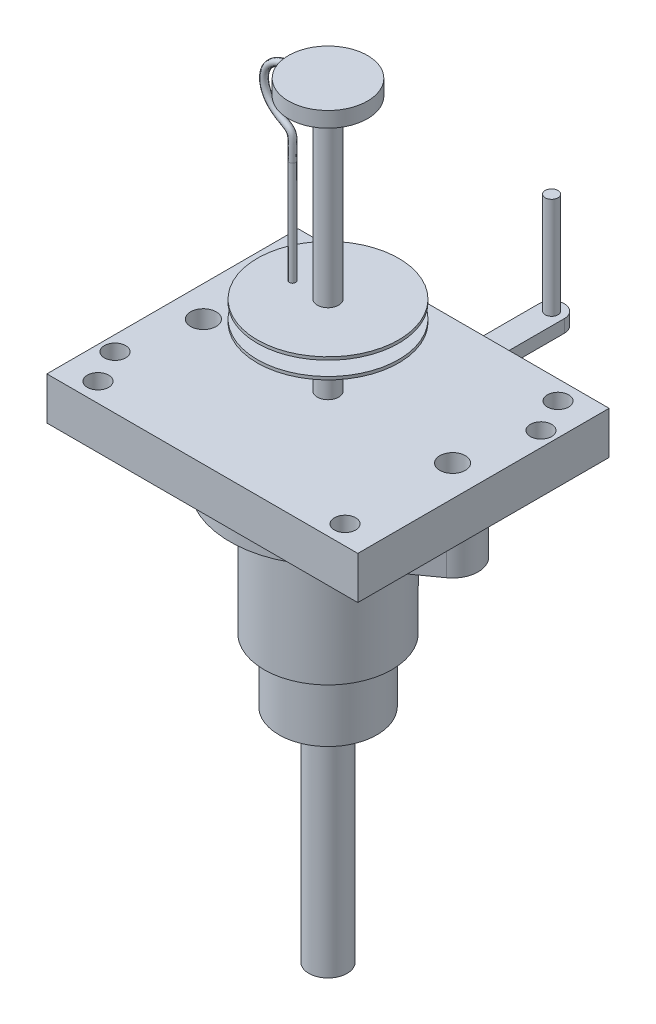
SolidWorks part; units mm, degrees
ref_plane "Front Plane" through (0, 0, 0) normal (0, 0, 1) x (1, 0, 0)
ref_plane "Top Plane" through (0, 0, 0) normal (0, 1, 0) x (1, 0, 0)
ref_plane "Right Plane" through (0, 0, 0) normal (1, 0, 0) x (0, 0, -1)
sketch "Sketch1" plane through (0, 0, 0) normal (0, 1, 0) x (1, 0, 0)
  line L1 (-36.5, -29.5) -> (36.5, -29.5)
  line L2 (-36.5, -29.5) -> (-36.5, 29.5)
  line L3 (-36.5, 29.5) -> (36.5, 29.5)
  line L4 (36.5, -29.5) -> (36.5, 29.5)
  line L5 (-36.5, -29.5) -> (36.5, 29.5) construction
  line L6 (-36.5, 29.5) -> (36.5, -29.5) construction
  point P0 (0, 0)
  dimension "D1" = 59
  dimension "D2" = 73
extrude "Boss-Extrude1" add sketch "Sketch1" against normal blind 10
sketch "Sketch2" plane through (0, 0, 0) normal (0, 1, 0) x (1, 0, 0)
  circle A0 centre (0, 0) radius 2.5
  dimension "D1" = 5
extrude "Boss-Extrude2" add sketch "Sketch2" along normal blind 60
sketch "Sketch3" plane through (0, 60, 0) normal (0, 1, 0) x (1, 0, 0)
  circle A0 centre (0, 0) radius 9.275
  dimension "D1" = 18.55
extrude "Boss-Extrude3" add sketch "Sketch3" along normal blind 3.6
ref_plane "Plane1" through (0, 14, 0) normal (0, 1, 0) x (1, 0, 0)
sketch "Sketch4" plane through (0, 14, 0) normal (0, 1, 0) x (1, 0, 0)
  circle A0 centre (0, 0) radius 16.6
  dimension "D1" = 33.2
extrude "Boss-Extrude4" add sketch "Sketch4" along normal blind 0.7
ref_plane "Plane2" through (0, 18, 0) normal (0, 1, 0) x (1, 0, 0)
sketch "Sketch5" plane through (0, 18, 0) normal (0, 1, 0) x (1, 0, 0)
  circle A1 centre (0, 0) radius 16.6 construction
  circle A2 centre (0, 0) radius 16.6
extrude "Boss-Extrude5" add sketch "Sketch5" along normal blind 0.7
sketch "Sketch7" plane through (0, -10, 0) normal (0, -1, 0) x (1, 0, 0)
  line L0 (32.25, -10.1714) -> (32.25, 9.148) construction
  line L1 (-19.7854, 27.5) -> (-31.5, 27.5) construction
  line L2 (-31.5, 21.4228) -> (-31.5, 27.5) construction
  line L3 (-36.5, -29.5) -> (-36.5, 29.5) construction
  line L4 (-36.5, 29.5) -> (36.5, 29.5) construction
  line L5 (0, 0) -> (-68.4596, 0) construction
  line L6 (0, 0) -> (0, -32.3752) construction
  line L7 (35.5, -19.5) -> (35.5, -7.1912) construction
  line L8 (26.5899, -19.5) -> (35.5, -19.5) construction
  line L9 (36.5, -29.5) -> (-36.5, -29.5) construction
  line L10 (36.5, 29.5) -> (36.5, -29.5) construction
  line L11 (-32.25, -10.1714) -> (-32.25, 9.148) construction
  line L12 (-35.5, 19.5) -> (-35.5, 7.1912) construction
  line L13 (-26.5899, 19.5) -> (-35.5, 19.5) construction
  circle A0 centre (-29, 25) radius 2.5
  circle A1 centre (29, 25) radius 2.5
  circle A2 centre (-29, -25) radius 2.5
  circle A3 centre (29, -25) radius 2.5
  circle A4 centre (33, -17) radius 2.5
  circle A5 centre (29.25, 0) radius 3
  circle A7 centre (-29.25, 0) radius 3
  circle A8 centre (-33, 17) radius 2.5
  dimension "D1" = 5
  dimension "D2" = 5
  dimension "D4" = 5
  dimension "D7" = 6
  dimension "D3" = 2
  dimension "D5" = 10
  dimension "D6" = 1
  dimension "D8" = 58.5
  dimension "D9" = 2
  dimension "D10" = 64.5
  dimension "D11" = 1
  dimension "D12" = 10
extrude "Cut-Extrude1" cut sketch "Sketch7" against normal up to surface (10 mm away) up to face at (0, 0, -2.5)
sketch "Sketch8" plane through (0, -10, 0) normal (0, -1, 0) x (1, 0, 0)
  line L0 (0, 0) -> (0, -27.931) construction
  line L1 (32.7372, 4.8826) -> (13.3675, 18.7166)
  line L2 (0, 0) -> (-51.9039, 0) construction
  line L3 (32.7372, -4.8826) -> (13.3675, -18.7166)
  line L4 (-32.7372, 4.8826) -> (-13.3675, 18.7166)
  line L5 (-32.7372, -4.8826) -> (-13.3675, -18.7166)
  arc A0 (13.3675, 18.7166) -> (-13.3675, 18.7166) centre (0, 0) ccw
  circle A1 centre (-29.25, 0) radius 3 construction
  arc A3 (-32.7372, 4.8826) -> (-32.7372, -4.8826) centre (-29.25, 0) ccw
  arc A4 (32.7372, 4.8826) -> (32.7372, -4.8826) centre (29.25, 0) cw
  arc A5 (-13.3675, -18.7166) -> (13.3675, -18.7166) centre (0, 0) ccw
  circle A6 centre (29.25, 0) radius 3 construction
  circle A7 centre (29.25, 0) radius 3
  circle A8 centre (-29.25, 0) radius 3
  dimension "D1" = 46
  dimension "D2" = 12
extrude "Boss-Extrude6" add sketch "Sketch8" along normal blind 9.15
sketch "Sketch9" plane through (0, -19.15, 0) normal (0, -1, 0) x (1, 0, 0)
  circle A0 centre (0, 0) radius 15
  dimension "D1" = 30
extrude "Boss-Extrude7" add sketch "Sketch9" along normal blind 30
sketch "Sketch10" plane through (0, -19.15, 0) normal (0, -1, 0) x (1, 0, 0)
  circle A0 centre (0, 0) radius 11.5
  dimension "D1" = 23
extrude "Boss-Extrude8" add sketch "Sketch10" along normal blind 45
sketch "Sketch11" plane through (0, -19.15, 0) normal (0, -1, 0) x (1, 0, 0)
  circle A0 centre (0, 0) radius 4.5
  dimension "D1" = 9
extrude "Boss-Extrude9" add sketch "Sketch11" along normal blind 97
chamfer "Chamfer1" distance 2 angle 45 1 edges at (0, -19.15, 15)
sketch "Sketch12" plane through (0, -10, 0) normal (0, -1, 0) x (1, 0, 0)
  line L0 (0, 0) -> (0, -41.2) construction
  line L1 (36.5, -29.5) -> (-36.5, -29.5) construction
  line L3 (3, -52.5) -> (3, -29.5)
  line L5 (-3, -52.5) -> (-3, -29.5)
  line L6 (15, -24.5) -> (-15, -24.5)
  line L7 (15, -24.5) -> (15, -29.5)
  line L8 (15, -29.5) -> (3, -29.5)
  line L9 (-15, -24.5) -> (-15, -29.5)
  line L10 (15, -24.5) -> (-15, -29.5) construction
  line L11 (15, -29.5) -> (-15, -24.5) construction
  line L12 (14.6438, -55.5) -> (-27.7787, -55.5) construction
  line L13 (-3, -29.5) -> (-15, -29.5)
  arc A1 (-3, -52.5) -> (3, -52.5) centre (0, -52.5) ccw
  point P2 (0, -27)
  dimension "D1" = 6
  dimension "D2" = 26
  dimension "D3" = 30
  dimension "D4" = 5
extrude "Boss-Extrude10" add sketch "Sketch12" along normal blind 3
sketch "Sketch13" plane through (0, -10, 0) normal (0, 1, 0) x (1, 0, 0)
  circle A0 centre (0, 52.5) radius 1.5
  arc A1 (3, 52.5) -> (-3, 52.5) centre (0, 52.5) ccw construction
  arc A2 (3, 52.5) -> (-3, 52.5) centre (0, 52.5) ccw
  dimension "D1" = 3
extrude "Boss-Extrude11" add sketch "Sketch13" along normal blind 23.8 contours A0 region at (0, -10, -52.5)
ref_axis "Axis1" through (0, 60, 0) along (0, -1, 0)
ref_plane "ThermocoupleAngle" through (0, 0, 0) normal (0.0523, 0, 0.9986) x (0, -1, 0)
sketch "Sketch17" plane through (0, 0, 0) normal (0.0523, 0, 0.9986) x (0, -1, 0)
  line L0 (-63.6, -9.275) -> (-60, -9.275) construction
  line L2 (-43.1018, -7.9222) -> (0, -7.9222)
  line L3 (0, -37.9939) -> (0, 34.9061) construction
  line L4 (-62.2019, -9.275) -> (-62.4174, -8.0525)
  line L5 (-63.6, -9.275) -> (-60, -9.275) construction
  line L8 (-73.2922, -18.775) -> (-20.8832, -18.775) construction
  line L13 (-63.6, -9.275) -> (-60, -9.275) construction
  line L14 (-62.9405, -9.4052) -> (-63.156, -8.1827)
  line L15 (-43.1018, -8.6722) -> (0, -8.6722) construction
  line L16 (-61.4633, -9.1448) -> (-61.6788, -7.9222)
  line L17 (-43.1018, -7.1722) -> (0, -7.1722) construction
  spline S0 degree 3 poles (-62.2019, -9.275) (-61.0998, -15.5251) (-53.7952, -15.3644) (-48.7362, -7.4677) (-48.6925, -7.9222) (-43.1018, -7.9222) knots 0 0 0 0 0.529649 0.629649 1 1 1 1
  spline S1 degree 1 poles (-62.9405, -9.4052) (-43.1018, -8.6722) knots 0 0 1 1 construction
  spline S2 degree 3 poles (-62.9405, -9.4052) (-62.8734, -9.7856) (-62.6906, -10.5607) (-62.1886, -11.8878) (-61.2986, -13.2591) (-59.8968, -14.3821) (-57.7428, -15.1852) (-55.4134, -15.023) (-53.2405, -14.0831) (-51.756, -13.0334) (-50.5036, -11.6148) (-49.5918, -10.2046) (-48.9757, -9.3112) (-48.5653, -8.927) (-48.155, -8.7489) (-47.3711, -8.6608) (-46.4205, -8.6486) (-45.5318, -8.6547) (-44.6234, -8.6651) (-43.7979, -8.6709) (-43.3291, -8.6722) (-43.1018, -8.6722) knots 0 0 0 0 0.03125 0.0625 0.125 0.1875 0.25 0.375 0.4375 0.5 0.5625 0.625 0.6875 0.75 0.8125 0.875 0.90625 0.9375 0.96875 0.984375 1 1 1 1 construction
  spline S3 degree 1 poles (-61.4633, -9.1448) (-43.1018, -7.1722) knots 0 0 1 1 construction
  spline S4 degree 3 poles (-61.4633, -9.1448) (-61.4066, -9.4662) (-61.25, -10.1292) (-60.8411, -11.2029) (-60.1562, -12.247) (-59.1429, -13.0543) (-57.9696, -13.496) (-56.6724, -13.5896) (-55.3168, -13.3431) (-53.9856, -12.769) (-52.7608, -11.9015) (-51.7299, -10.7396) (-50.8561, -9.4028) (-50.1914, -8.4177) (-49.4472, -7.6568) (-48.4185, -7.2443) (-47.4315, -7.1631) (-46.4188, -7.1482) (-45.5145, -7.1549) (-44.6087, -7.1651) (-43.7901, -7.171) (-43.3267, -7.1722) (-43.1018, -7.1722) knots 0 0 0 0 0.03125 0.0625 0.125 0.1875 0.25 0.3125 0.375 0.4375 0.5 0.5625 0.625 0.6875 0.75 0.8125 0.875 0.90625 0.9375 0.96875 0.984375 1 1 1 1 construction
  point P24 (-62.9634, -9.275)
  dimension "D1" = 80
  dimension "D2" = 0.75
  dimension "D3" = 0.75
sketch "Sketch19" plane through (0, 0, 0) normal (0, 1, 0) x (1, 0, 0)
  circle A0 centre (-7.9114, -0.4146) radius 0.75
  dimension "D1" = 1.5
sweep "Sweep1" add profiles "Sketch19" path "Sketch17"
